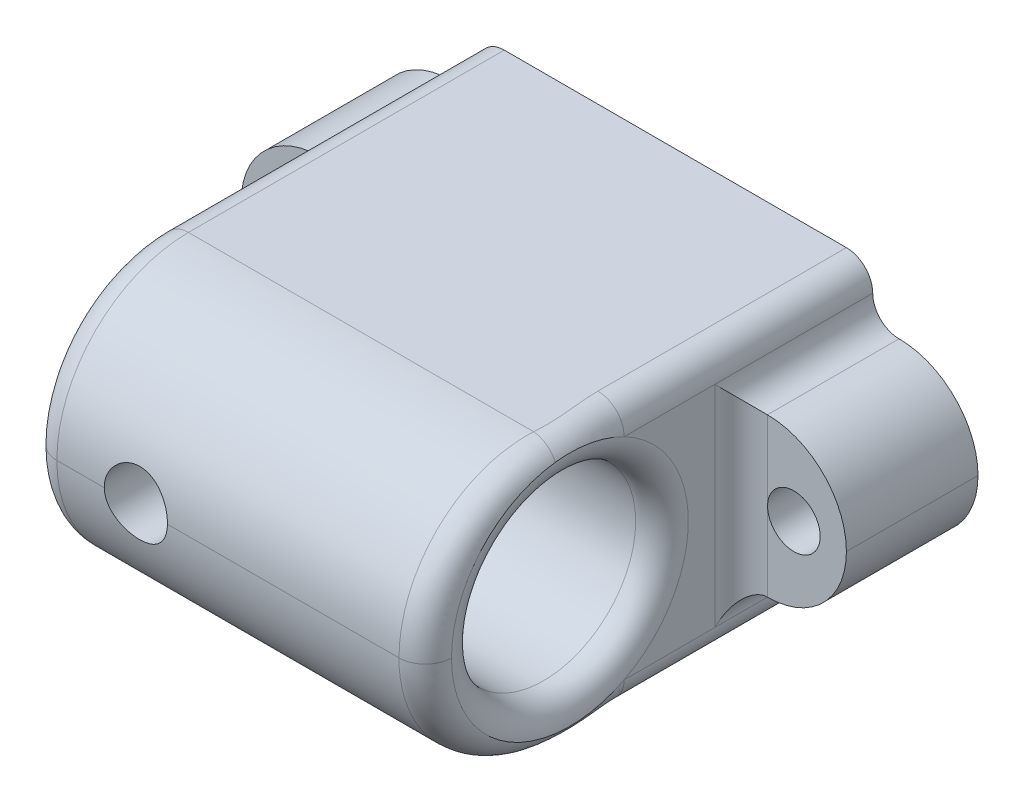
SolidWorks part; units mm, degrees
ref_plane "Front Plane" through (0, 0, 0) normal (0, 0, 1) x (1, 0, 0)
ref_plane "Top Plane" through (0, 0, 0) normal (0, 1, 0) x (1, 0, 0)
ref_plane "Right Plane" through (0, 0, 0) normal (1, 0, 0) x (0, 0, -1)
sketch "Sketch1" plane through (3.8956, 0, 0) normal (0, 0, 1) x (1, 0, 0)
  line L1 (0, 0) -> (15, 0)
  line L2 (0, 0) -> (0, -10)
  line L3 (0, -10) -> (15, -10)
  line L4 (15, 0) -> (15, -10)
extrude "Boss-Extrude1" add sketch "Sketch1" along normal blind 17
fillet "Fillet5" radius 5 2 edges at (11.3956, 0, 17) (11.3956, -10, 17)
sketch "Sketch7" plane through (18.8956, 0, 1.6286) normal (1, 0, 0) x (0, 0, -1)
  circle A0 centre (-9.8771, -5) radius 3.5
extrude "Cut-Extrude1" cut sketch "Sketch7" against normal blind 15
fillet "Fillet6" radius 1 1 edges at (18.8956, -5, 8.0057)
hole_wizard "CBORE for M2 Pan Head Machine Screw3" positions "3DSketch9" profile "Sketch16" counterbore size "M2" standard "ANSI Metric" end condition through all
sketch3d "3DSketch9"
  point P0 (7.8976, -4.9742, 0)
sketch "Sketch16" plane through (7.8976, -4.9742, 0) normal (1, 0, 0) x (0, 1, 0)
  line L0 (0, 0) -> (0, 17)
  line L1 (0, 17) -> (1.2, 17)
  line L3 (1.2, 17) -> (1.2, 1.6)
  line L4 (2.5, 1.6) -> (1.2, 1.6)
  line L5 (2.5, 1.6) -> (2.5, 0.025)
  line L6 (2.5, 0.025) -> (2.525, 0)
  line L7 (2.525, 0) -> (0, 0)
  line L8 (-2.5, 0.025) -> (-2.525, 0) construction
  line L11 (0, -6.35) -> (0, 107.95) construction
  dimension "Thru Hole Dia." = 2.4
  dimension "Thru Hole Depth" = 17
  dimension "C'Bore Dia." = 5
  dimension "C'Bore Depth" = 1.6
  dimension "Near C'Sink Dia." = 5.05
  dimension "Near C'Sink Angle" = 90
sketch "Sketch18" plane through (18.8956, 0, 0) normal (1, 0, 0) x (0, 0, -1)
  line L0 (0, -10) -> (0, 0) construction
  line L2 (0, -5) -> (0, -2)
  line L3 (0, -2) -> (-5, -2)
  line L4 (-5, -5) -> (-5, -2)
  line L7 (0, -5) -> (0, -8)
  line L8 (0, -8) -> (-5, -8)
  line L9 (-5, -5) -> (-5, -8)
extrude "Boss-Extrude3" add sketch "Sketch18" along normal blind 4 contours L4 L3 L2 L7 L8 L9
fillet "Fillet12" radius 3 2 edges at (22.8956, -2, 2.5) (22.8956, -8, 2.5)
pattern_linear "LPattern15" count 2 spacing 19 along (-1, 0, 0) of "Boss-Extrude3"
fillet "Fillet14" radius 3 2 edges at (-0.1044, -8, 2.5) (-0.1044, -2, 2.5)
fillet "Fillet15" radius 1 8 edges at (3.8956, -10, 6) (3.8956, -8.5355, 15.5355) (3.8956, -1.4645, 15.5355) (18.8956, 0, 6) (18.8956, -10, 6) (3.8956, 0, 6) (18.8956, -1.4645, 15.5355) (18.8956, -8.5355, 15.5355)
sketch "Sketch21" plane through (0, 0, 5) normal (0, 0, 1) x (1, 0, 0)
  circle A1 centre (20.9, -5) radius 1
extrude "Cut-Extrude2" cut sketch "Sketch21" against normal through all both and the other way through all
pattern_linear "LPattern16" count 2 spacing 19.1 along (-1, 0, 0) of "Cut-Extrude2"
fillet "Fillet17" radius 1 2 edges at (3.8956, -2, 2.5) (3.8956, -8, 2.5)
fillet "Fillet18" radius 1 2 edges at (18.8956, -2, 2.5) (18.8956, -8, 2.5)
fillet "Fillet19" radius 1 1 edges at (18.8956, -5, 5)
fillet "Fillet20" radius 1 1 edges at (3.8956, -5, 5)
